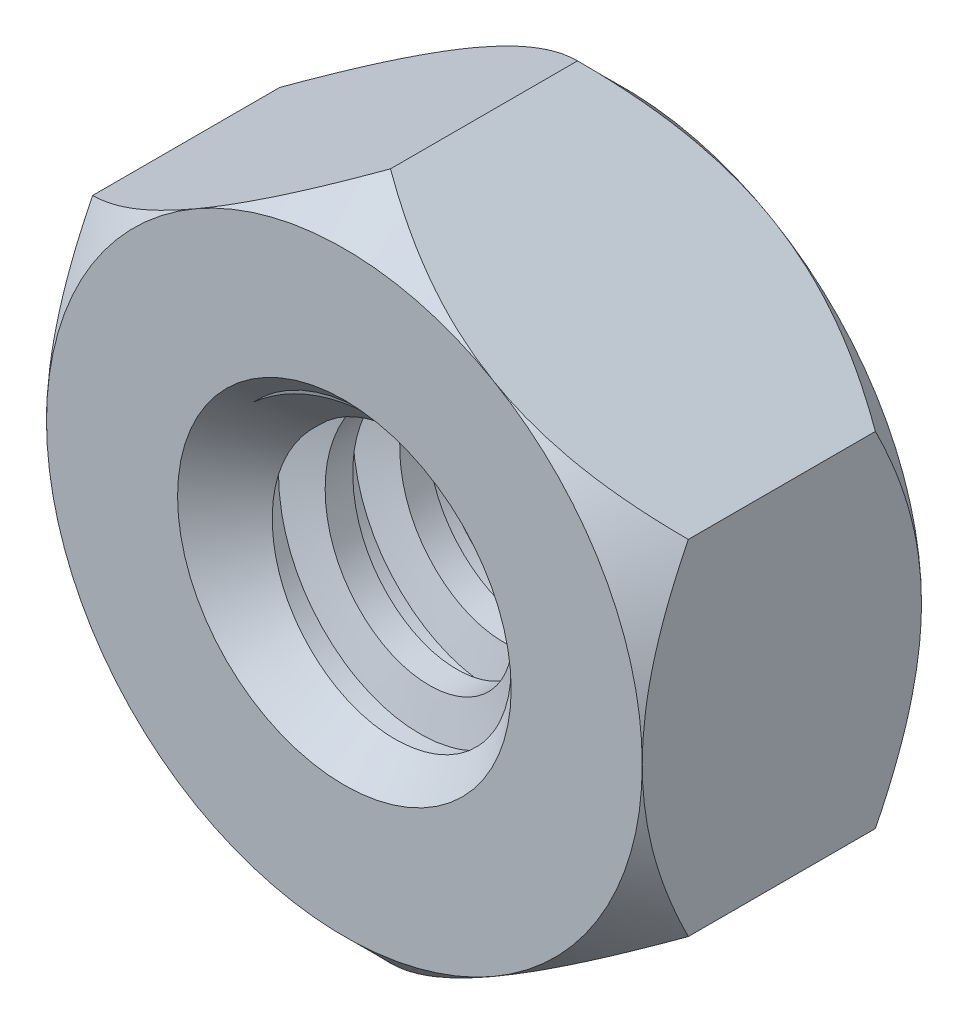
SolidWorks part; units mm, degrees
note: The reader was unsure of these and kept them because the rebuilt part matched: shared geometry of "Sketch4<2>", "Sketch5<2>".
ref_plane "Front" through (0, 0, 0) normal (0, 0, 1) x (1, 0, 0)
ref_plane "Top" through (0, 0, 0) normal (0, 1, 0) x (1, 0, 0)
ref_plane "Right" through (0, 0, 0) normal (1, 0, 0) x (0, 0, -1)
sketch "Sketch1" plane through (0, 0, 0) normal (0, 0, 1) x (1, 0, 0)
  line L1 (0, -7.3323) -> (6.35, -3.6662)
  line L2 (6.35, -3.6662) -> (6.35, 3.6662)
  line L3 (6.35, 3.6662) -> (0, 7.3323)
  line L4 (0, 7.3323) -> (-6.35, 3.6662)
  line L5 (-6.35, 3.6662) -> (-6.35, -3.6662)
  line L6 (-6.35, -3.6662) -> (0, -7.3323)
  circle A0 centre (0, 0) radius 6.35 construction
  circle A1 centre (0, 0) radius 3.175
  dimension "Width" = 12.7
  dimension "ThreadDia" = 6.35
extrude "Boss-Extrude1" add sketch "Sketch1" along normal mid plane 5.9531
sketch "Sketch2" plane through (0, 0, 2.9766) normal (0, 0, 1) x (1, 0, 0)
  circle A0 centre (0, 0) radius 3.175 construction
  circle A1 centre (0, 0) radius 3.175
curve "Helix/Spiral1" pitch 1.5875 height 7.5406 radius 3.175 centre (0, 0, 2.9766) axis (0, 0, -1) start towards (0, 1, 0) parameters "Pitch"=1.5875
sketch "Sketch3" plane through (0, 0, 0) normal (1, 0, 0) x (0, 0, -1)
  line L0 (-2.9766, 3.175) -> (-3.1818, 2.3813)
  line L1 (-2.9766, 3.6662) -> (-2.9766, -3.6662) construction
  line L2 (-2.9766, 3.175) -> (-2.9766, -3.175) construction
  line L3 (-3.1818, 2.3813) -> (-3.7703, 2.3813)
  line L4 (-3.7703, 2.3813) -> (-3.9756, 3.175)
  line L5 (-3.9756, 3.175) -> (-2.9766, 3.175)
  line L6 (-3.8729, 2.7782) -> (-3.0792, 2.7782) construction
  line L7 (-3.4761, 2.7782) -> (-3.4761, 2.3813) construction
  spline S0 degree 3 poles (-2.9766, 3.175) (-2.9437, 3.175) (-2.8772, 3.0097) (-2.7782, 2.3035) (-2.6789, 1.2467) (-2.5797, 0) (-2.4805, -1.2467) (-2.3813, -2.3035) (-2.282, -3.0097) (-2.1828, -3.2577) (-2.0836, -3.0097) (-1.9844, -2.3035) (-1.8852, -1.2467) (-1.7859, 0) (-1.6867, 1.2467) (-1.5875, 2.3035) (-1.4883, 3.0097) (-1.3891, 3.2577) (-1.2898, 3.0097) (-1.1906, 2.3035) (-1.0914, 1.2467) (-0.9922, 0) (-0.893, -1.2467) (-0.7938, -2.3035) (-0.6945, -3.0097) (-0.5953, -3.2577) (-0.4961, -3.0097) (-0.3969, -2.3035) (-0.2977, -1.2467) (-0.1984, 0) (-0.0992, 1.2467) (0, 2.3035) (0.0992, 3.0097) (0.1984, 3.2577) (0.2977, 3.0097) (0.3969, 2.3035) (0.4961, 1.2467) (0.5953, 0) (0.6945, -1.2467) (0.7937, -2.3035) (0.893, -3.0097) (0.9922, -3.2577) (1.0914, -3.0097) (1.1906, -2.3035) (1.2898, -1.2467) (1.3891, 0) (1.4883, 1.2467) (1.5875, 2.3035) (1.6867, 3.0097) (1.7859, 3.2577) (1.8852, 3.0097) (1.9844, 2.3035) (2.0836, 1.2467) (2.1828, 0) (2.282, -1.2467) (2.3813, -2.3035) (2.4805, -3.0097) (2.5797, -3.2577) (2.6789, -3.0097) (2.7781, -2.3035) (2.8773, -1.2467) (2.9766, 0) (3.0758, 1.2467) (3.175, 2.3035) (3.2742, 3.0097) (3.3734, 3.2577) (3.4727, 3.0097) (3.5719, 2.3035) (3.6711, 1.2467) (3.7703, 0) (3.8695, -1.2467) (3.9688, -2.3035) (4.068, -3.0097) (4.1672, -3.2576) (4.2664, -3.0098) (4.3657, -2.3032) (4.4647, -1.2479) (4.5312, -0.413) (4.5641, 0) knots 0 0 0 0 0.013158 0.026316 0.039474 0.052632 0.065789 0.078947 0.092105 0.105263 0.118421 0.131579 0.144737 0.157895 0.171053 0.184211 0.197368 0.210526 0.223684 0.236842 0.25 0.263158 0.276316 0.289474 0.302632 0.315789 0.328947 0.342105 0.355263 0.368421 0.381579 0.394737 0.407895 0.421053 0.434211 0.447368 0.460526 0.473684 0.486842 0.5 0.513158 0.526316 0.539474 0.552632 0.565789 0.578947 0.592105 0.605263 0.618421 0.631579 0.644737 0.657895 0.671053 0.684211 0.697368 0.710526 0.723684 0.736842 0.75 0.763158 0.776316 0.789474 0.802632 0.815789 0.828947 0.842105 0.855263 0.868421 0.881579 0.894737 0.907895 0.921053 0.934211 0.947368 0.960526 0.973684 0.986842 1 1 1 1 construction
  dimension "D1" = 29
  dimension "D2" = 0.5885
  dimension "D3" = 0.7937
sketch "Sketch4" plane through (0, 0, 2.9766) normal (0, 0, 1) x (1, 0, 0)
  circle A0 centre (0, 0) radius 3.556
  circle A1 centre (0, 0) radius 3.175 construction
  dimension "D1" = 0.381
sketch "Sketch5" plane through (0, 0, -2.9766) normal (0, 0, -1) x (-1, 0, 0)
  circle A1 centre (0, 0) radius 3.556
  circle A2 centre (0, 0) radius 3.556
  dimension "D1" = 0
sweep "Sweep1" add profiles "Sketch3" path "Helix/Spiral1"
extrude "Cut-Extrude1" cut sketch "Sketch4" along normal through all
extrude "Cut-Extrude2" cut sketch "Sketch5" along normal through all
extrude "Cut-Extrude3" cut sketch "Sketch4<2>" against normal through all draft 45
sketch "Sketch4<2>" plane through (0, 0, 2.9766) normal (0, 0, 1) x (1, 0, 0) same geometry as "Sketch4"
extrude "Cut-Extrude4" cut sketch "Sketch5<2>" against normal through all draft 45
sketch "Sketch5<2>" plane through (0, 0, -2.9766) normal (0, 0, -1) x (-1, 0, 0) same geometry as "Sketch5"
sketch "Sketch6" plane through (0, 0, 2.9766) normal (0, 0, 1) x (1, 0, 0)
  line L0 (-6.35, 0) -> (0, 0) construction
  line L2 (-6.35, 3.6662) -> (-6.35, -3.6662) construction
  circle A0 centre (0, 0) radius 6.35
extrude "Cut-Extrude5" cut sketch "Sketch6" against normal through all draft 45 flip side to cut
sketch "Sketch7" plane through (0, 0, -2.9766) normal (0, 0, -1) x (-1, 0, 0)
  circle A1 centre (0, 0) radius 6.35
  circle A2 centre (0, 0) radius 6.35
  dimension "D1" = 0
extrude "Cut-Extrude6" cut sketch "Sketch7" against normal through all draft 45 flip side to cut
equation "\"D3@Helix/Spiral1\" = \"Height@Boss-Extrude1\"+\"Pitch@Helix/Spiral1\""
equation "\"D2@Sketch3\" = \"Pitch@Helix/Spiral1\"*.3707"
equation "\"D3@Sketch3\" = \"Pitch@Helix/Spiral1\"*.5"
